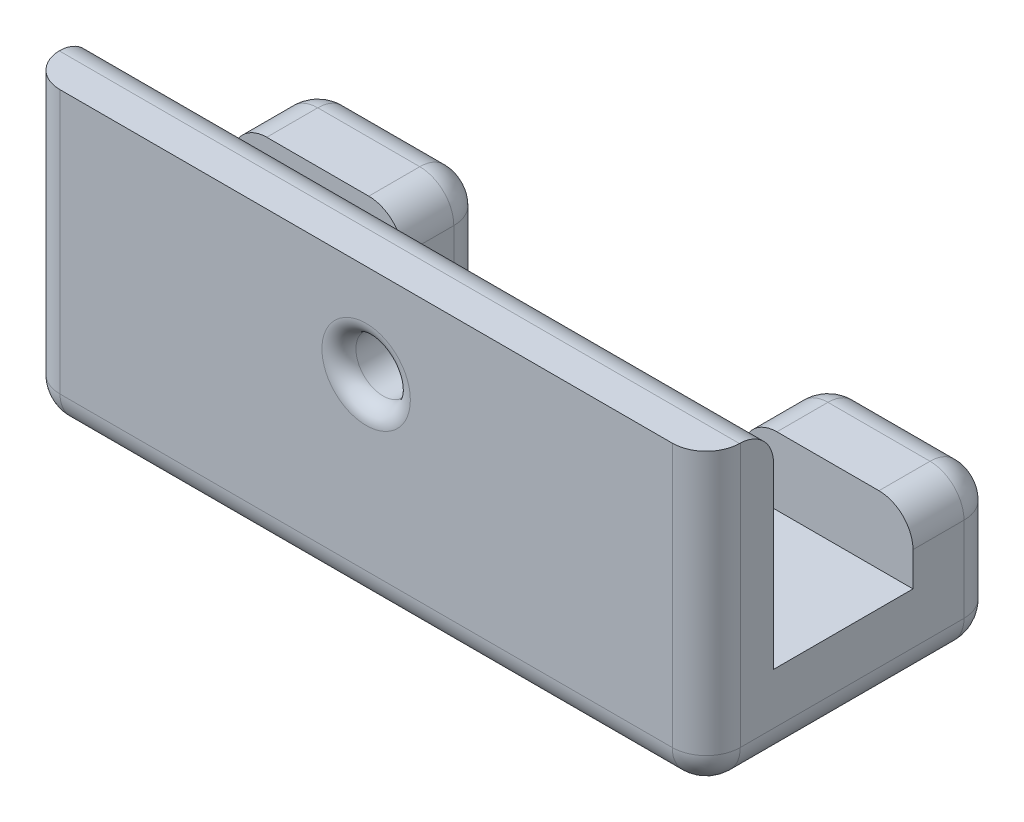
SolidWorks part; units mm, degrees
ref_plane "Front Plane" through (0, 0, 0) normal (0, 0, 1) x (1, 0, 0)
ref_plane "Top Plane" through (0, 0, 0) normal (0, 1, 0) x (1, 0, 0)
ref_plane "Right Plane" through (0, 0, 0) normal (1, 0, 0) x (0, 0, -1)
sketch "Sketch1" plane through (0, 0, 0) normal (0, 1, 0) x (1, 0, 0)
  line L0 (-44.6146, -25.9209) -> (-14.6146, -25.9209)
  line L1 (-14.6146, -35.876) -> (-44.6146, -35.876)
  line L2 (-4.6146, -23.7209) -> (-4.6146, -35.876)
  line L3 (-44.6146, -23.7209) -> (-34.6146, -23.7209)
  line L4 (-34.6146, -25.9209) -> (-34.6146, -18.7209)
  line L5 (-44.6146, -18.7209) -> (-34.6146, -18.7209)
  line L6 (-44.6146, -18.7209) -> (-44.6146, -30.9209)
  line L7 (-4.6146, -35.876) -> (-14.6146, -35.876)
  line L8 (-14.6146, -18.7209) -> (-14.6146, -30.9209)
  line L9 (-4.6146, -23.7209) -> (-4.6146, -18.7209)
  line L10 (-4.6146, -18.7209) -> (-14.6146, -18.7209)
  line L11 (-44.6146, -35.876) -> (-44.6146, -30.9209)
  line L12 (-14.6146, -30.9209) -> (-14.6146, -35.876)
  line L13 (-4.6146, -31.876) -> (-14.6146, -31.876)
  line L14 (-14.6146, -25.9209) -> (-4.6146, -25.9209)
  line L15 (-14.6146, -23.7209) -> (-4.6146, -23.7209)
  line L16 (-14.6146, -31.876) -> (-44.6146, -31.876)
extrude "Boss-Extrude1" add sketch "Sketch1" along normal blind 5 contours L8 L0 L6 | L8 L15 L9 L0 | L3 L6 L0 L4 | L12 L11 | L16 L11 | L2 L13 L12 L7 | L14 L8 L12 L13 L2 | L15 L8 L14 L2 | L5 L6 L3 L4 region at (-39.6146, 0, 24.8209) region at (-29.6146, 0, 28.8984) region at (-39.6146, 0, 21.2209) region at (-9.6146, 0, 28.8984) region at (-9.6146, 0, 24.8209) region at (-29.6146, 0, 33.876) region at (-9.6146, 0, 21.2209) region at (-9.6146, 0, 33.876)
extrude "Boss-Extrude2" add sketch "Sketch1<3>" along normal blind 9 contours L5 L6 L0 L4 | L8 L15 L9 L10 region at (-39.6146, 0, 21.2209) region at (-9.6146, 0, 21.2209)
sketch "Sketch1<3>" plane through (0, 0, 0) normal (0, 1, 0) x (1, 0, 0) same geometry as "Sketch1"
sketch "Sketch2" plane through (0, 5, 0) normal (0, 1, 0) x (1, 0, 0)
  line L0 (-4.6146, -35.876) -> (-4.6146, -31.9209)
  line L4 (-44.6146, -31.9209) -> (-44.6146, -35.876)
  line L5 (-44.6146, -31.9209) -> (-4.6146, -31.9209)
  line L6 (-44.6146, -35.876) -> (-4.6146, -35.876)
  line L8 (-44.6146, -35.876) -> (-4.6146, -35.876)
  line L10 (-44.6146, -31.9209) -> (-44.6146, -35.876)
  line M3 (-44.6146, -23.7209) -> (-44.6146, -35.876)
  line M32 (-44.6146, -35.876) -> (-4.6146, -35.876)
  line M37 (-4.6146, -35.876) -> (-4.6146, -23.7209)
extrude "Boss-Extrude4" add sketch "Sketch2" along normal blind 12.5 contours L5 M3 M32 M37 region at (-24.6146, 5, 33.8984)
fillet "Fillet1" radius 2 21 edges at (-14.6146, 9, 21.2209) (-44.6146, 4.5, 18.7209) (-4.6146, 9, 21.2209) (-4.6146, 8.75, 35.876) (-24.6146, 0, 35.876) (-44.6146, 8.75, 35.876) (-44.6146, 0, 27.2984) (-4.6146, 0, 27.2984) (-44.6146, 9, 21.2209) (-34.6146, 9, 21.2209) (-4.6146, 4.5, 18.7209) (-9.6146, 9, 18.7209) (-34.6146, 4.5, 18.7209) (-39.6146, 9, 18.7209) (-9.6146, 0, 18.7209) (-14.6146, 4.5, 18.7209) (-39.6146, 0, 18.7209) (-34.6146, 0, 22.3209) (-14.6146, 0, 22.3209) (-24.6146, 5, 25.9209) (-24.6146, 0, 25.9209)
sketch "Sketch6" plane through (0, 0, 31.9209) normal (0, 0, -1) x (-1, 0, 0)
  line L0 (24.6146, 5) -> (24.6146, 12)
  line L1 (44.6146, 5) -> (4.6146, 5) construction
  circle A0 centre (24.6146, 12) radius 1.6
extrude "Cut-Extrude1" cut sketch "Sketch6" against normal up to surface (3.9551 mm away) contours A0 region at (-25.714, 10.9006, 31.9209) up to face at (-24.6146, 9.75, 35.876)
fillet "Fillet2" radius 1 2 edges at (-23.0146, 12, 35.876) (-26.2146, 12, 31.9209)
fillet "Fillet3" radius 2 1 edges at (-24.6146, 17.5, 31.9209)
